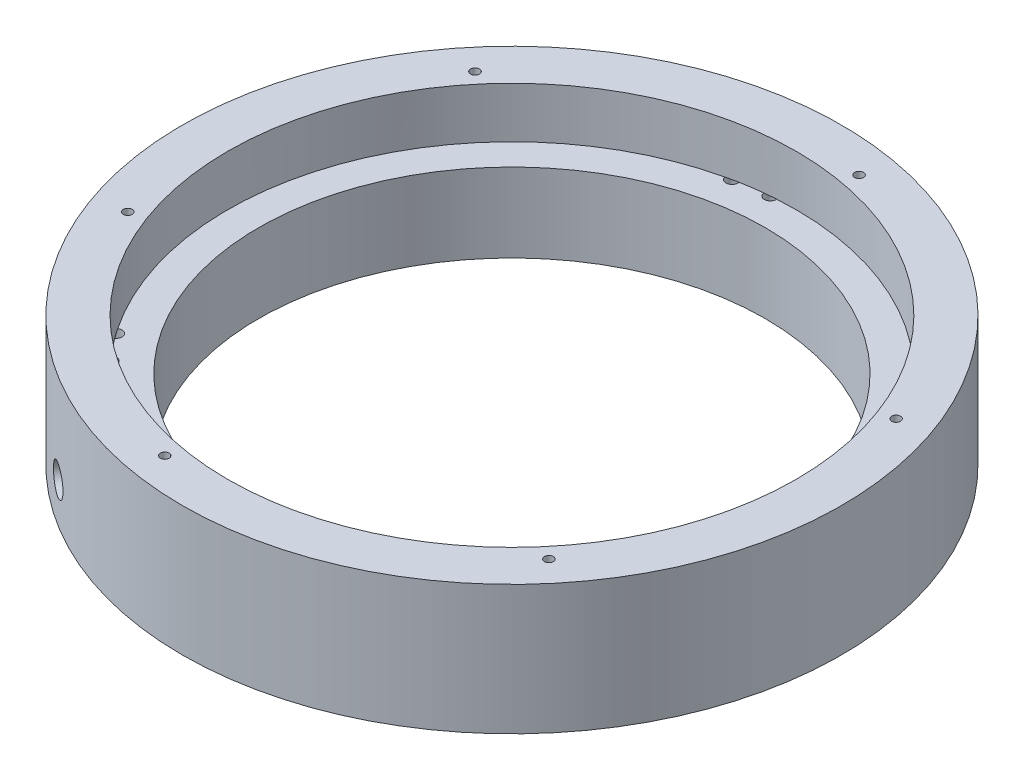
SolidWorks part; units mm, degrees
material "6061 Alloy"
ref_plane "Front Plane" through (0, 0, 0) normal (0, 0, 1) x (1, 0, 0)
ref_plane "Top Plane" through (0, 0, 0) normal (0, 1, 0) x (1, 0, 0)
ref_plane "Right Plane" through (0, 0, 0) normal (1, 0, 0) x (0, 0, -1)
sketch "Sketch1" plane through (0, 0, 0) normal (0, 1, 0) x (1, 0, 0)
  line L0 (26.3001, -61.9592) -> (0, 0) construction
  line L1 (0, 0) -> (0, -32.7983) construction
  line L2 (0, 0) -> (58.126, -27.1046) construction
  line L3 (0, 0) -> (-15.1655, -86.0079) construction
  line L4 (0, 0) -> (84.7676, -52.9687) construction
  circle A0 centre (0, 0) radius 57.15
  circle A1 centre (0, 0) radius 74.3712
  circle A3 centre (0, 0) radius 64.135
  circle A4 centre (-11.7434, -66.6001) radius 1.0033
  circle A5 centre (26.3001, -61.9592) radius 1.9939
  circle A6 centre (26.3001, -61.9592) radius 5.5626
  circle A7 centre (58.126, -27.1046) radius 1.3589
  circle A8 centre (60.9305, -20.0194) radius 1.3589
  dimension "D1" = 114.3
  dimension "D5" = 2.0066
  dimension "D7" = 3.9878
  dimension "D9" = 11.1252
  dimension "D10" = 2.7178
  dimension "D2" = 148.7424
  dimension "D4" = 67.6275
  dimension "D6" = 67.31
  dimension "D8" = 23
  dimension "D11" = 65
  dimension "D15" = 58
  dimension "D12" = 7.62
  dimension "D13" = 10
  dimension "D3" = 6.985
extrude "Boss-Extrude1" add sketch "Sketch1" along normal blind 17.78 contours A7 A3 A6 A0 | A3 A6 A5 | A5 | A3 A6 | A1 A7 A3 A6 A4 | A3 A7 | A3 A7 | A3 A8 | A3 A8 region at (-72.2677, 0, 0) region at (61.6385, 0, 9.1979) region at (24.6668, 0, 58.1114) region at (25.119, 0, 59.1766) region at (61.4759, 0, 20.1987) region at (60.3801, 0, 19.8386) region at (57.601, 0, 26.8598) region at (58.6464, 0, 27.3473) region at (26.3001, 0, 61.9592)
extrude "Boss-Extrude3" add sketch "Sketch1<3>" along normal blind 11.43 from surface contours A1 A7 A3 A6 A4 | A3 A6 A5 | A5 | A3 A7 | A3 A8 region at (-72.2677, 0, 0) region at (25.119, 0, 59.1766) region at (61.4759, 0, 20.1987) region at (58.6464, 0, 27.3473) region at (26.3001, 0, 61.9592) starting at face at (0, 17.78, 57.15)
sketch "Sketch1<3>" plane through (0, 0, 0) normal (0, 1, 0) x (1, 0, 0) same geometry as "Sketch1"
pattern_circular "CirPattern1" count 6 over 360 about axis through (0, 29.21, 0) along (0, 1, 0) of face at (-11.7434, 0, 67.6034)
sketch "Sketch2" plane through (0, 0, 0) normal (1, 0, 0) x (0, 0, -1)
  line L0 (-57.15, 0) -> (57.15, 0) construction
  line L1 (57.15, 17.78) -> (-57.15, 17.78) construction
  line L2 (-57.15, 0) -> (57.15, 0)
  line L3 (57.15, 17.78) -> (-57.15, 17.78)
  line L4 (91.6697, 17.018) -> (97.1828, 17.018) construction
  line L5 (0, 17.78) -> (0, 35.8369)
  circle A0 centre (60.6425, 18.6055) radius 1.5875 construction
  circle A1 centre (60.6425, 18.669) radius 1.651
  dimension "D2" = 3.175
  dimension "D4" = 3.302
  dimension "D1" = 60.6425
  dimension "D3" = 0.762
extrude "Cut-Extrude2" cut sketch "Sketch1<4>" along normal blind 0.635 contours A3 A6 A5 | A3 A6 | A6 region at (24.6668, 0, 58.1114) region at (25.119, 0, 59.1766)
sketch "Sketch1<4>" plane through (0, 0, 0) normal (0, 1, 0) x (1, 0, 0) same geometry as "Sketch1"
extrude "Cut-Extrude3" cut sketch "Sketch1<5>" along normal blind 6.35 contours A5 region at (26.3001, 0, 61.9592)
sketch "Sketch1<5>" plane through (0, 0, 0) normal (0, 1, 0) x (1, 0, 0) same geometry as "Sketch1"
pattern_circular "CirPattern3" count 3 over 360 about axis through (0, 0, 0) along (0, 1, 0) of face at (26.3001, 6.35, 63.9531) of face at (26.3001, 6.35, 63.9531) of face at (26.3001, 0.635, 63.9531) of face at (26.3001, 0.635, 67.5218)
ref_plane "Plane1" through (0, 0, 0) normal (-0.5299, 0, 0.848) x (0.848, 0, 0.5299)
sketch "Sketch3" plane through (0, 0, 0) normal (-0.5299, 0, 0.848) x (0.848, 0, 0.5299)
  line L0 (57.15, 17.78) -> (-57.15, 17.78) construction
  line L1 (57.15, 17.78) -> (-57.15, 17.78)
  line L2 (0, 0) -> (0, 17.78) construction
  circle A0 centre (0, 8.89) radius 3.3528
  circle A1 centre (0, 8.89) radius 3.9751
  dimension "D1" = 6.7056
  dimension "D3" = 7.9502
  dimension "D2" = 8.89
extrude "Cut-Extrude5" cut sketch "Sketch3" along normal up to surface (74.2956 mm away) contours L2 A0 | A0 L2 region at (-1.2067, 8.89, -0.7541) region at (1.2067, 8.89, 0.7541) up to face at (0, 0, 74.3712)
extrude "Cut-Extrude13" cut sketch "Sketch1<6>" along normal up to surface (17.78 mm away) contours A3 A8 | A3 A8 | A7 region at (61.4759, 0, 20.1987) region at (60.3801, 0, 19.8386) up to face at (0, 17.78, 57.15)
sketch "Sketch1<6>" plane through (0, 0, 0) normal (0, 1, 0) x (1, 0, 0) same geometry as "Sketch1"
pattern_circular "CirPattern4" count 3 over 360 about axis through (0, 0, 0) along (0, 1, 0) of "Cut-Extrude13"
equation "\"Middle Coupler Inner Daimeter\"= 3.875in"
equation "\"Middle Coupler  Wall Thickness\" = 0.25in"
equation "\"Middle Coupler Bottom Thickness\"= 0.2in"
equation "\"Bearing Rail Offset\"= 0.45in"
equation "\"3-56 UNF Tap\"= 0.089in"
equation "\"3-56 UNF Clearance\"= 0.104in"
equation "\"Ball Bearing Distance\"= 0.03in"
equation "\"D1@Sketch1\"=\"Middle Coupler Inner Daimeter\"+0.625in"
equation "\"D3@Sketch1\"=0.275"
equation "\"D4@Sketch1\"=\"Middle Coupler Inner Daimeter\"/2+0.625/2+0.275+0.275/2"
equation "\"D5@Sketch1\"=\"3-48 Tap\""
equation "\"D1@Sketch2\"=\"Middle Coupler Inner Daimeter\"/2in + \"Bearing Rail Offset\""
equation "\"D3@Sketch2\"=\"Ball Bearing Distance\""
equation "\"D4@Sketch2\"=\"D2@Sketch2\"+0.005"
equation "\"D1@Boss-Extrude3\"=0.320in+0.01in + 0.03*4"
equation "\"TCA Outer Diameter\" = 6in"
equation "\"Interstage Aeroframe Wall Thickness\" = 0.072in"
equation "\"Compression Spring OD\"= 0.42in"
equation "\"10-24 Tap\"= 0.157in"
equation "\"10-24 Clearance\"= 0.196in"
equation "\"Lower Stage Fuselage Wall Thickness\" = 0.25in"
equation "\"6-32 Tap\" = 0.107in"
equation "\"D10@Sketch1\"=\"6-32 Tap\""
equation "\"1/4-20 Tap\" = 0.201in"
equation "\"D1@Sketch3\"=0.254 + 0.01"
equation "\"12-24 Tap\" = 0.177in"
equation "\"D3@Sketch3\"=0.313"
equation "\"3-48 Tap\"= 0.079in"
equation "\"3-48 Clearance\" = 0.104in"
equation "\"6-32 Clearance\" = 0.144"
equation "\"D2@Sketch1\"=\"TCA Outer Diameter\"-\"Interstage Aeroframe Wall Thickness\"*2"
equation "\"D6@Sketch1\"=(\"Middle Coupler Inner Daimeter\"+\"TCA Outer Diameter\"+0.5+0.0125*2in)/4 + 0.05"
